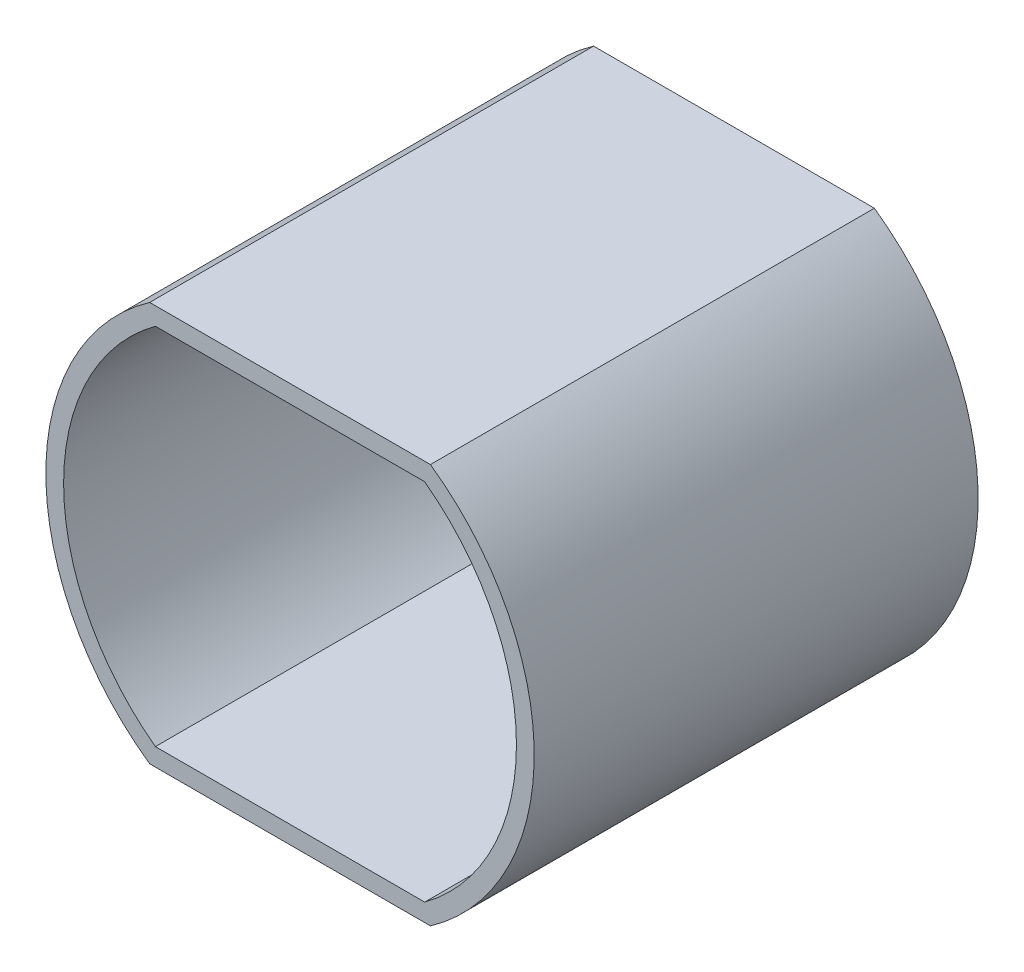
SolidWorks part; units mm, degrees
ref_plane "Front Plane" through (0, 0, 0) normal (0, 0, 1) x (1, 0, 0)
ref_plane "Top Plane" through (0, 0, 0) normal (0, 1, 0) x (1, 0, 0)
ref_plane "Right Plane" through (0, 0, 0) normal (1, 0, 0) x (0, 0, -1)
sketch "Sketch2" plane through (0, 0, 0) normal (0, 0, 1) x (1, 0, 0)
  line L3 (15.8114, 22.5) -> (-15.8114, 22.5)
  line L5 (15.8114, -22.5) -> (-15.8114, -22.5)
  arc A1 (15.8114, -22.5) -> (15.8114, 22.5) centre (0, 0) ccw
  arc A2 (-15.8114, 22.5) -> (-15.8114, -22.5) centre (0, 0) ccw
  circle A3 centre (0, 0) radius 2
extrude "Boss-Extrude8" add sketch "Sketch2" along normal blind 50
shell "Shell4" thickness 2 removed face at (2, 0, 50) removed face at (0, 0, 50)
